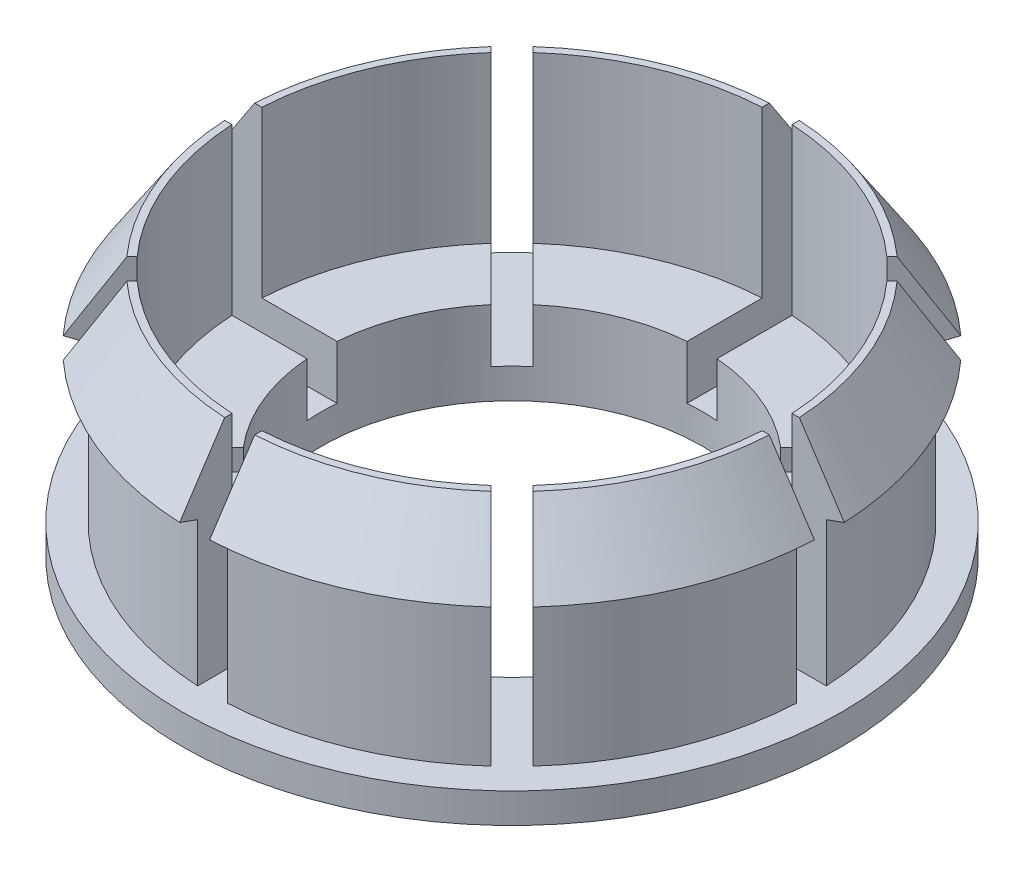
SolidWorks part; units mm, degrees
ref_plane "Front Plane" through (0, 0, 0) normal (0, 0, 1) x (1, 0, 0)
ref_plane "Top Plane" through (0, 0, 0) normal (0, 1, 0) x (1, 0, 0)
ref_plane "Right Plane" through (0, 0, 0) normal (1, 0, 0) x (0, 0, -1)
sketch "Sketch5" plane through (0, 0, 0) normal (0, 0, 1) x (1, 0, 0)
  line L0 (-11.25, -3.5) -> (-11.25, 3.5)
  line L1 (11.25, 3.5) -> (-11.25, 3.5) construction
  line L2 (11.25, 3.5) -> (11.25, -3.5) construction
  line L3 (11.25, -3.5) -> (-11.25, -3.5) construction
  line L4 (-11.25, 3.5) -> (-11.25, -3.5) construction
  line L5 (11.25, 3.5) -> (-11.25, -3.5) construction
  line L6 (11.25, -3.5) -> (-11.25, 3.5) construction
  line L7 (-11.25, 3.5) -> (-11.557, 3.5)
  line L8 (-11.557, 3.5) -> (-13.462, 0.6023)
  line L9 (-13.462, 0.6023) -> (-12.7, 0.325)
  line L10 (-12.7, 0.325) -> (-12.7, -5.775)
  line L11 (-12.7, -5.775) -> (-13.97, -5.775)
  line L12 (-13.97, -5.775) -> (-13.97, -7.045)
  line L13 (-13.97, -7.045) -> (-8.075, -7.045)
  line L14 (-8.075, -7.045) -> (-8.075, -3.5)
  line L15 (-8.075, -3.5) -> (-11.25, -3.5)
  line L16 (0, 0.325) -> (0, -8.827) construction
  line L17 (8.075, -7.045) -> (-8.075, -7.045) construction
  line L18 (8.075, -7.045) -> (8.075, -3.5) construction
  line L19 (8.075, -3.5) -> (-8.075, -3.5) construction
  line L20 (-8.075, -7.045) -> (-8.075, -3.5) construction
  line L21 (8.075, -7.045) -> (-8.075, -3.5) construction
  line L22 (8.075, -3.5) -> (-8.075, -7.045) construction
  line L23 (12.7, -5.775) -> (-12.7, -5.775) construction
  line L24 (12.7, -5.775) -> (12.7, 0.325) construction
  line L25 (12.7, 0.325) -> (-12.7, 0.325) construction
  line L26 (-12.7, -5.775) -> (-12.7, 0.325) construction
  line L27 (12.7, -5.775) -> (-12.7, 0.325) construction
  line L28 (12.7, 0.325) -> (-12.7, -5.775) construction
  point P0 (0, 0)
  point P7 (0, -5.2725)
  point P19 (0, -2.725)
  dimension "D1" = 7
  dimension "D2" = 22.5
  dimension "D3" = 3.175
  dimension "D4" = 6.1
  dimension "D5" = 3.175
  dimension "D6" = 25.4
  dimension "D7" = 0.762
  dimension "D8" = 1.905
  dimension "D9" = 1.27
  dimension "D10" = 1.27
  dimension "D11" = 70
revolve "Revolve1" add sketch "Sketch5" angle 360 about L16
sketch "Sketch6" plane through (0, 3.5, 0) normal (0, 1, 0) x (1, 0, 0)
  line L1 (0.635, 0) -> (-0.635, 0)
  line L2 (0.635, 0) -> (0.635, 13.462)
  line L3 (0.635, 13.462) -> (-0.635, 13.462)
  line L4 (-0.635, 0) -> (-0.635, 13.462)
  line L5 (0.635, 0) -> (-0.635, 13.462) construction
  line L6 (0.635, 13.462) -> (-0.635, 0) construction
  circle A0 centre (0, 0) radius 13.462 construction
  point P0 (0, 6.731)
  dimension "D1" = 1.27
extrude "Cut-Extrude3" cut sketch "Sketch6" against normal up to surface (9.275 mm away) and the other way through all up to face at (0, -5.775, 13.97)
ref_axis "Axis1" through (0, 4.0728, 0) along (0, -1, 0)
pattern_circular "CirPattern1" count 8 over 360 about axis through (0, 4.0728, 0) along (0, -1, 0) of "Cut-Extrude3"
